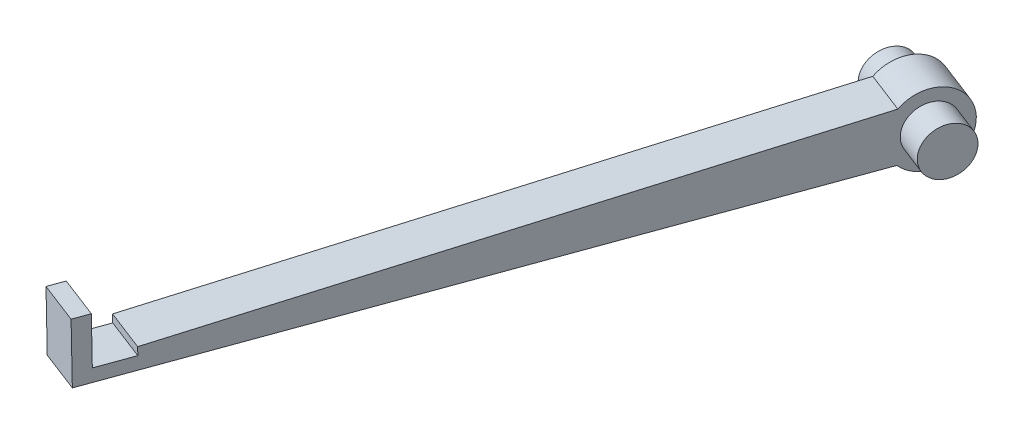
SolidWorks part; units mm, degrees
ref_plane "Plan de face" through (0, 0, 0) normal (0, 0, 1) x (1, 0, 0)
ref_plane "Plan de dessus" through (0, 0, 0) normal (0, 1, 0) x (1, 0, 0)
ref_plane "Plan de droite" through (0, 0, 0) normal (1, 0, 0) x (0, 0, -1)
sketch "Esquisse1" plane through (-65.3001, -64.8105, 252.6924) normal (0.9327, 0, 0.3607) x (-0.0058, 0.9999, 0.0151)
  line L0 (-10.803, -115.9093) -> (-12.598, -78.3419)
  line L1 (-13.9058, -78.3769) -> (-13.9058, -75.0956)
  line L4 (-13.9058, -75.0956) -> (-10.0868, -75.0956)
  line L5 (-10.0868, -75.0956) -> (-10.0868, -76.0956)
  line L6 (-13.9058, -115.812) -> (-13.9058, -78.3769)
  line L7 (-10.0868, -76.0956) -> (-13.098, -76.0956)
  line L8 (-13.098, -78.3419) -> (-12.598, -78.3419)
  line L9 (-13.098, -76.0956) -> (-13.098, -78.3419)
  arc A1 (-14.0086, -115.9093) -> (-10.803, -115.9093) centre (-12.4058, -117.5) ccw
  circle A2 centre (-12.4058, -117.5) radius 2.2582
  dimension "D1" = 1
  dimension "D2" = 0.5
extrude "BASE" add sketch "Esquisse1" along normal blind 1.4 and the other way blind 1.4 contours A1 A2 | A2 A1 L8 L6 region at (-29.9289, -75.954, 161.2208) region at (-22.8551, -75.3108, 142.9276)
sketch "Esquisse2" plane through (29.5032, 0, 11.4086) normal (0.9327, 0, 0.3607) x (0.3607, 0, -0.9327)
  arc A1 (-142.5902, -76.3925) -> (-142.6247, -74.2634) centre (-141.5509, -75.3108) ccw construction
  arc A2 (-142.5902, -76.3925) -> (-142.6247, -74.2634) centre (-141.5509, -75.3108) ccw
  circle A3 centre (-141.5509, -75.3108) radius 1.5
extrude "BOSS BLOC G" add sketch "Esquisse2" along normal blind 1.9 contours A2 A3 region at (-21.5493, -75.3108, 143.4325)
sketch "Esquisse3" plane through (26.8916, 0, 10.3988) normal (-0.9327, 0, -0.3607) x (-0.3607, 0, 0.9327)
  arc A0 (142.6247, -74.2634) -> (142.5902, -76.3925) centre (141.5509, -75.3108) ccw construction
  arc A1 (142.6247, -74.2634) -> (142.5902, -76.3925) centre (141.5509, -75.3108) ccw
  circle A2 centre (141.5509, -75.3108) radius 1.5
extrude "BOSS BLOC D" add sketch "Esquisse3" along normal blind 1.9 contours A1 A2 region at (-24.1608, -75.3108, 142.4227)
